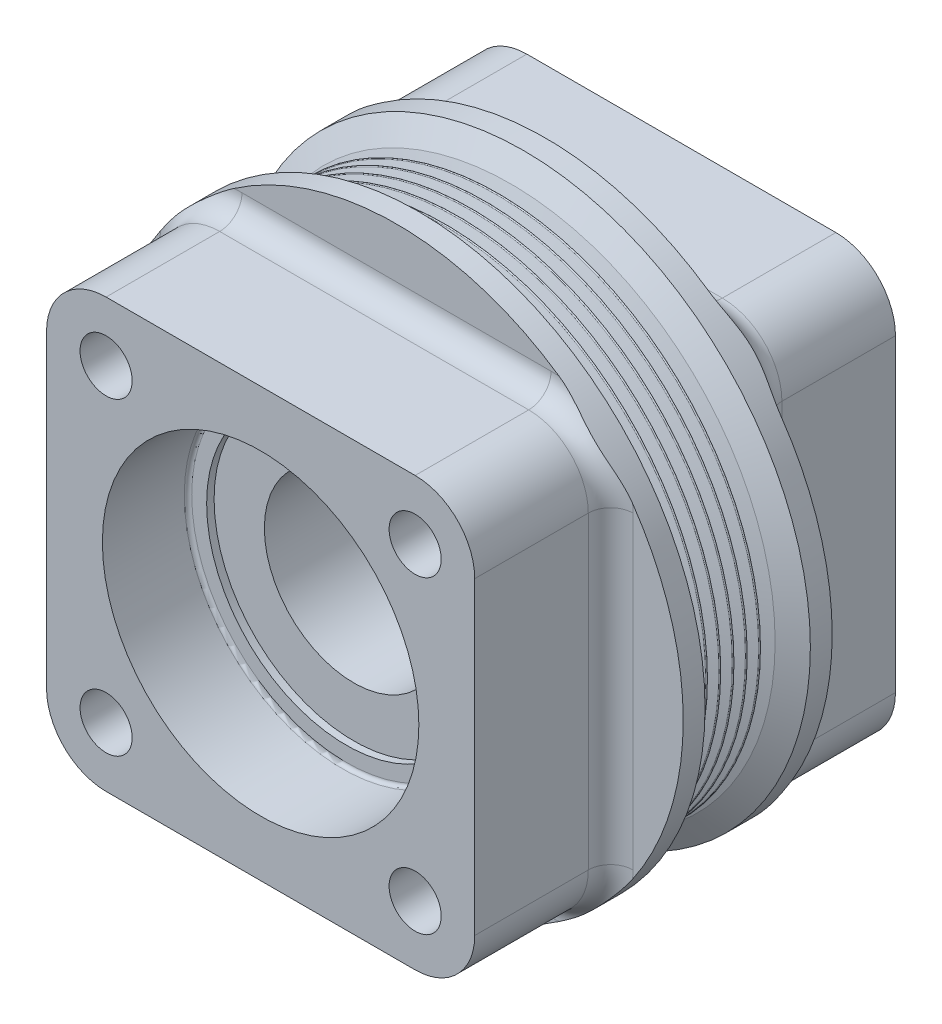
SolidWorks part; units mm, degrees
material "AISI 4340 Aço recozido"
ref_plane "Plano frontal" through (0, 0, 0) normal (0, 0, 1) x (1, 0, 0)
ref_plane "Plano superior" through (0, 0, 0) normal (0, 1, 0) x (1, 0, 0)
ref_plane "Plano direito" through (0, 0, 0) normal (1, 0, 0) x (0, 0, -1)
sketch "Esboço2" plane through (0, 0, 0) normal (0, 0, 1) x (1, 0, 0)
  line L1 (-41.5, -57.5) -> (41.5, -57.5)
  line L2 (-57.5, -41.5) -> (-57.5, 41.5)
  line L3 (-41.5, 57.5) -> (41.5, 57.5)
  line L4 (57.5, -41.5) -> (57.5, 41.5)
  line L5 (-57.5, -57.5) -> (57.5, 57.5) construction
  line L6 (-57.5, 57.5) -> (57.5, -57.5) construction
  arc A0 (-41.5, -57.5) -> (-57.5, -41.5) centre (-41.5, -41.5) cw
  arc A1 (41.5, -57.5) -> (57.5, -41.5) centre (41.5, -41.5) ccw
  arc A2 (41.5, 57.5) -> (57.5, 41.5) centre (41.5, 41.5) cw
  arc A3 (-57.5, 41.5) -> (-41.5, 57.5) centre (-41.5, 41.5) cw
  circle A4 centre (0, 0) radius 42.5
  circle A5 centre (0, 0) radius 25
  point P0 (0, 0)
  point P21 (0, 0)
  dimension "D2" = 16
  dimension "D3" = 85
  dimension "D4" = 50
  dimension "D1" = 115
sketch "Esboço3" plane through (0, 0, 0) normal (1, 0, 0) x (0, 0, -1)
  line L0 (20, 0) -> (20, 77)
  line L1 (20, 77) -> (14.1441, 77)
  line L3 (8.4302, 67.4004) -> (7.3549, 70.3546)
  line L4 (6.8851, 70.3546) -> (5.8098, 67.4004)
  line L5 (4.8702, 67.4004) -> (3.7949, 70.3546)
  line L6 (3.3251, 70.3546) -> (2.2498, 67.4004)
  line L7 (1.3102, 67.4004) -> (0.2349, 70.3546)
  line L8 (-0.2349, 70.3546) -> (-1.3102, 67.4004)
  line L9 (-2.2498, 67.4004) -> (-3.3251, 70.3546)
  line L10 (-3.7949, 70.3546) -> (-4.8702, 67.4004)
  line L11 (-5.8098, 67.4004) -> (-6.8851, 70.3546)
  line L12 (-7.3549, 70.3546) -> (-8.4302, 67.4004)
  line L14 (-14.1441, 77) -> (-20, 77)
  line L15 (-20, 77) -> (-20, 0)
  line L16 (-20, 0) -> (20, 0)
  line L17 (-10.68, 71) -> (10.68, 71) construction
  line L18 (-20, 77) -> (-20, 200)
  line L19 (0, 0) -> (51.063, 0) construction
  line L20 (-9.3698, 67.4004) -> (-10.68, 71)
  line L21 (-10.68, 71) -> (-14.1441, 77)
  line L22 (9.3698, 67.4004) -> (10.68, 71)
  line L23 (10.68, 71) -> (14.1441, 77)
  line L24 (-20, 200) -> (20, 200)
  line L25 (14.1441, 77) -> (20, 87.1427)
  line L26 (20, 87.1427) -> (20, 77)
  line L27 (-14.1441, 77) -> (-20, 87.1427)
  line L28 (-20, 87.1427) -> (-20, 77)
  line L29 (20, 200) -> (20, 77)
  line L30 (20, 77) -> (75, 77)
  line L31 (75, 77) -> (75, 127)
  line L32 (75, 127) -> (-75, 127)
  line L33 (-75, 127) -> (-75, 77)
  line L34 (-75, 77) -> (-20, 77)
  arc A0 (-6.8851, 70.3546) -> (-7.3549, 70.3546) centre (-7.12, 70.269) ccw
  arc A1 (-3.3251, 70.3546) -> (-3.7949, 70.3546) centre (-3.56, 70.269) ccw
  arc A2 (0.2349, 70.3546) -> (-0.2349, 70.3546) centre (0, 70.269) ccw
  arc A3 (3.7949, 70.3546) -> (3.3251, 70.3546) centre (3.56, 70.269) ccw
  arc A4 (7.3549, 70.3546) -> (6.8851, 70.3546) centre (7.12, 70.269) ccw
  arc A5 (9.3698, 67.4004) -> (8.4302, 67.4004) centre (8.9, 67.5714) cw
  arc A6 (5.8098, 67.4004) -> (4.8702, 67.4004) centre (5.34, 67.5714) cw
  arc A7 (2.2498, 67.4004) -> (1.3102, 67.4004) centre (1.78, 67.5714) cw
  arc A8 (-1.3102, 67.4004) -> (-2.2498, 67.4004) centre (-1.78, 67.5714) cw
  arc A9 (-4.8702, 67.4004) -> (-5.8098, 67.4004) centre (-5.34, 67.5714) cw
  arc A10 (-8.4302, 67.4004) -> (-9.3698, 67.4004) centre (-8.9, 67.5714) cw
  point P2 (-7.12, 71)
  point P24 (-7.12, 71)
  point P27 (0, 0)
  point P31 (-71.4427, 75.5)
  point P32 (0, 127)
  point P36 (-7.12, 71)
  point P39 (-3.56, 71)
  point P42 (0, 71)
  point P45 (3.56, 71)
  point P48 (7.12, 71)
  point P54 (5.34, 66.1095)
  point P57 (1.78, 66.1095)
  point P60 (-1.78, 66.1095)
  point P63 (-5.34, 66.1095)
  dimension "D1" = 0.5
  dimension "D2" = 0.25
  dimension "D3" = 40
  dimension "D4" = 40
  dimension "D5" = 20
  dimension "D6" = 3.56
  dimension "D7" = 60
  dimension "D8" = 30
  dimension "D9" = 142
  dimension "D10" = 6
  dimension "D11" = 200
  dimension "D12" = 150
  dimension "D13" = 50
extrude "EXTRUSÃO QUADRADO" add sketch "Esboço2" along normal mid plane 113 contours L3 A2 L4 A1 L1 A0 L2 A3
revolve "REVOLUÇÃO POLIA" add sketch "Esboço3" angle 360 about L16 region at (0, 36.1147, 0)
revolve "CORTE REVOLUÇÃO POLIA" cut sketch "Esboço3<4>" angle 360 about L19 region at (0, 80.3809, -18.048) region at (0, 102, -47.5) region at (0, 99.8952, 0) region at (0, 80.3809, 18.048) region at (0, 102, 47.5)
sketch "Esboço3<4>" plane through (0, 0, 0) normal (1, 0, 0) x (0, 0, -1) same geometry as "Esboço3"
sketch "Esboço4" plane through (0, 0, 0) normal (0, 0, 1) x (1, 0, 0)
  circle A0 centre (0, 0) radius 24
  circle A1 centre (0, 0) radius 42.5
  circle A2 centre (0, 0) radius 27
  circle A3 centre (0, 0) radius 37.5
  dimension "D1" = 85
  dimension "D2" = 48
  dimension "D3" = 75
  dimension "D4" = 54
extrude "FURO EIXO PASSANTE" cut sketch "Esboço4<5>" against normal through all both and the other way through all contours A0
sketch "Esboço4<5>" plane through (0, 0, 0) normal (0, 0, 1) x (1, 0, 0) same geometry as "Esboço4"
extrude "REBAIXO ROLAMENTO 1" cut sketch "Esboço4" along normal offset from surface (23 mm away) 23 from surface contours A1 up to face at (24, 0, -56.5) starting at face at (24, 0, -56.5)
extrude "REBAIXO ROLAMENTO 2" cut sketch "Esboço4<4>" against normal blind 23 from surface contours A1 starting at face at (24, 0, 56.5)
sketch "Esboço4<4>" plane through (0, 0, 0) normal (0, 0, 1) x (1, 0, 0) same geometry as "Esboço4"
extrude "Corte-extrusão4" cut sketch "Esboço4<6>" against normal blind 2 from surface contours A3 starting at face at (-42.5, 0, 33.5)
sketch "Esboço4<6>" plane through (0, 0, 0) normal (0, 0, 1) x (1, 0, 0) same geometry as "Esboço4"
extrude "Corte-extrusão5" cut sketch "Esboço4<7>" along normal blind 2 from surface contours A3 starting at face at (-42.5, 0, -33.5)
sketch "Esboço4<7>" plane through (0, 0, 0) normal (0, 0, 1) x (1, 0, 0) same geometry as "Esboço4"
hole_wizard "FUROS FIXAÇÃO 1" positions "Esboço7" profile "Esboço8" hole size "M16" standard "ISO"
sketch "Esboço7" plane through (0, 0, -56.5) normal (0, 0, -1) x (-1, 0, 0)
  line L1 (-41.5, -41.5) -> (41.5, -41.5)
  line L2 (-41.5, -41.5) -> (-41.5, 41.5)
  line L3 (-41.5, 41.5) -> (41.5, 41.5)
  line L4 (41.5, -41.5) -> (41.5, 41.5)
  line L5 (-41.5, -41.5) -> (41.5, 41.5) construction
  line L6 (-41.5, 41.5) -> (41.5, -41.5) construction
  point P18 (41.5, 41.5)
  point P83 (-41.5, -41.5)
  point P84 (-41.5, 41.5)
  point P85 (41.5, -41.5)
  point P99 (0, 0)
  dimension "D1" = 83
sketch "Esboço8" plane through (-41.5, 41.5, -56.5) normal (1, 0, 0) x (0, 1, 0)
  line L0 (0, 0) -> (0, 34.206)
  line L1 (0, 34.206) -> (7, 30)
  line L2 (7, 30) -> (7, 0)
  line L5 (7, 0) -> (0, 0)
  line L10 (0, 34.206) -> (-7, 30) construction
  line L11 (0, -6.35) -> (0, 107.95) construction
  dimension "Hole Dia." = 14
  dimension "Hole Depth" = 30
  dimension "Drill Angle" = 118
hole_wizard "FUROS FIXAÇÃO 2" positions "Esboço10" profile "Esboço11" hole size "M16" standard "ISO"
sketch "Esboço10" plane through (0, 0, 56.5) normal (0, 0, 1) x (1, 0, 0)
  point P0 (-41.5, 41.5)
  point P3 (41.5, 41.5)
  point P6 (41.5, -41.5)
  point P9 (-41.5, -41.5)
sketch "Esboço11" plane through (-41.5, 41.5, 56.5) normal (1, 0, 0) x (0, -1, 0)
  line L0 (0, 0) -> (0, 34.206)
  line L1 (0, 34.206) -> (7, 30)
  line L2 (7, 30) -> (7, 0)
  line L5 (7, 0) -> (0, 0)
  line L10 (0, 34.206) -> (-7, 30) construction
  line L11 (0, -6.35) -> (0, 107.95) construction
  dimension "Hole Dia." = 14
  dimension "Hole Depth" = 30
  dimension "Drill Angle" = 118
fillet "FILETE ALÍVIO" radius 6 16 edges at (52.8137, 52.8137, 20) (52.8137, -52.8137, 20) (-52.8137, 52.8137, 20) (-52.8137, -52.8137, 20) (57.5, 0, 20) (0, 57.5, 20) (-57.5, 0, 20) (0, -57.5, 20) (-52.8137, -52.8137, -20) (-52.8137, 52.8137, -20) (52.8137, -52.8137, -20) (52.8137, 52.8137, -20) (-57.5, 0, -20) (0, -57.5, -20) (57.5, 0, -20) (0, 57.5, -20)
fillet "Filete4" radius 1 2 edges at (-42.5, 0, -33.5) (-42.5, 0, 33.5)
equation "\"arma-espessura\"= 50                                                                    'disco arma - espessura disco arma"
equation "\"rolamento_D-ext\"= 85               'rolamento arma - diametro externo"
equation "\"rolamento_d-int\"= 45               'rolamento arma - diametro interno"
equation "\"rolamento_b-esp\"= 23               'rolamento arma - espessura"
equation "\"eixo_diam\"= \"rolamento_d-int\"      'eixo arma - diametro"
equation "\"camisa_largura\"=115                                                        'camisa arma - tamanho do lado"
equation "\"camisa_raio\"= 16                                                           'camisa arma - raio canto interno"
equation "\"D1@Esboço2\"=\"camisa_largura\""
equation "\"D2@Esboço2\"=\"camisa_raio\""
equation "\"D3@Esboço2\"=\"rolamento_D-ext\""
equation "\"D4@Esboço2\"=5+\"eixo_diam\""
equation "\"D1\" = \"rolamento_b-esp\" +  ( \"arma-espessura\" - \"rolamento_b-esp\" )  / 2"
equation "\"polia_diam_eff\"= 142"
equation "\"D9@Esboço3\"=\"polia_diam_eff\""
equation "\"escala\"= 1                        'projeto - escala geral"
equation "\"escala_disco-arma\"= 3                                                                  'disco arma - escala geometria disco arma"
equation "\"arma_eixo-furo_folga\"= 4                                                              'disco arma - folga entre furo arma e eixo"
equation "\"arma_rebaixo-camisa_raio\"= 12                                                         'disco arma - raio do rebaixo da camisa da arma "
equation "\"arma_rebaixo-camisa_b\"= \"rolamento_b-esp\" + (\"arma-espessura\"-\"rolamento_b-esp\")/2     'disco arma - profundidade rebaixo camisa"
equation "\"camisa_rebaixo_rolamento\"= 1 * \"rolamento_b-esp\""
equation "\"D1@EXTRUSÃO QUADRADO\" = \"camisa_comprimento-centro\""
equation "\"polia_espessura\"= 40  "
equation "\"D3@Esboço3\"=\"polia_espessura\""
equation "\"D1@Esboço4\"=\"rolamento_D-ext\""
equation "\"D2@Esboço4\"=\"rolamento_d-int\"+3"
equation "\"camisa_comprimento-centro\"= 2*(\"arma_rebaixo-camisa_b\")+\"polia_espessura\" "
equation "\"D1@REBAIXO ROLAMENTO 1\" = \"rolamento_b-esp\""
equation "\"D1@REBAIXO ROLAMENTO 2\" = \"camisa_rebaixo_rolamento\""
equation "\"camisa_furos_dist\"= 83"
equation "\"D1@Esboço7\"=\"camisa_furos_dist\""
equation "\"rolamento_D1-ext\"= 75             'rolamento arma - ressalto diam externo"
equation "\"rolamenot_d2-int\" = 54             'rolamento arma - ressalto diam interno"
equation "\"camisa_furos_prof\"= 30"
equation "\"camisa_raio-alivio\"= 6                                                    'camisa arma - raio de alivio de tensoes no encaixe da arma"
equation "\"D1@FILETE ALÍVIO\" = \"camisa_raio-alivio\""
equation "\"D3@Esboço4\"=\"rolamento_D1-ext\""
equation "\"D4@Esboço4\"=\"rolamenot_d2-int\""
